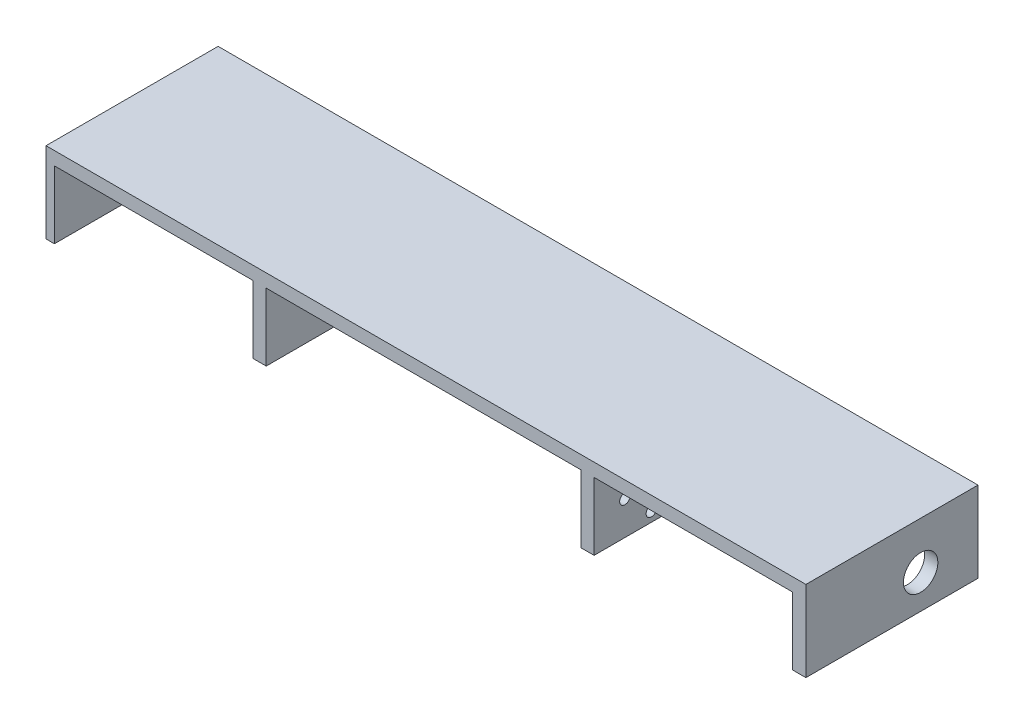
SolidWorks part; units mm, degrees
ref_plane "Front Plane" through (0, 0, 0) normal (0, 0, 1) x (1, 0, 0)
ref_plane "Top Plane" through (0, 0, 0) normal (0, 1, 0) x (1, 0, 0)
ref_plane "Right Plane" through (0, 0, 0) normal (1, 0, 0) x (0, 0, -1)
sketch "Sketch2" plane through (0, 0, 0) normal (0, 1, 0) x (1, 0, 0)
  line L1 (-42.6727, 74.2981) -> (244.3273, 74.2981)
  line L2 (-42.6727, 74.2981) -> (-42.6727, 9.2981)
  line L3 (-42.6727, 9.2981) -> (244.3273, 9.2981)
  line L4 (244.3273, 74.2981) -> (244.3273, 9.2981)
extrude "Boss-Extrude1" add sketch "Sketch2" along normal blind 5
sketch "Sketch4" plane through (0, 0, 0) normal (0, -1, 0) x (1, 0, 0)
  line L0 (-42.6727, -9.2981) -> (244.3273, -9.2981) construction
  line L1 (-42.6727, -74.2981) -> (-39.4977, -74.2981)
  line L2 (-42.6727, -74.2981) -> (-42.6727, -9.2981)
  line L3 (-42.6727, -9.2981) -> (-39.4977, -9.2981)
  line L4 (-39.4977, -74.2981) -> (-39.4977, -9.2981)
extrude "Boss-Extrude2" add sketch "Sketch4" along normal blind 25.5
sketch "Sketch5" plane through (0, 0, 0) normal (0, -1, 0) x (1, 0, 0)
  line L0 (-39.4977, -9.2981) -> (244.3273, -9.2981) construction
  line L1 (40.5023, -9.2981) -> (35.5023, -9.2981)
  line L2 (40.5023, -9.2981) -> (40.5023, -74.2981)
  line L3 (40.5023, -74.2981) -> (35.5023, -74.2981)
  line L4 (35.5023, -9.2981) -> (35.5023, -74.2981)
  line L5 (244.3273, -74.2981) -> (-39.4977, -74.2981) construction
  line L6 (-39.4977, -74.2981) -> (-39.4977, -9.2981) construction
  dimension "D1" = 80
  dimension "D2" = 5
extrude "Boss-Extrude3" add sketch "Sketch5" along normal blind 25.5 contours L2 L3 L4 L1
sketch "Sketch6" plane through (0, 0, 0) normal (0, -1, 0) x (1, 0, 0)
  line L0 (244.3273, -74.2981) -> (40.5023, -74.2981) construction
  line L1 (244.3273, -9.2981) -> (239.3273, -9.2981)
  line L2 (244.3273, -9.2981) -> (244.3273, -74.2981)
  line L3 (244.3273, -74.2981) -> (239.3273, -74.2981)
  line L4 (239.3273, -9.2981) -> (239.3273, -74.2981)
extrude "Boss-Extrude4" add sketch "Sketch6" along normal blind 25.5
sketch "Sketch7" plane through (-42.6727, 0, 0) normal (-1, 0, 0) x (0, 0, 1)
  line L0 (-9.2981, -25.5) -> (-74.2981, -25.5) construction
  line L1 (-9.2981, 5) -> (-9.2981, -25.5) construction
  circle A0 centre (-30.9648, -12.75) radius 3.5
  dimension "D3" = 7
  dimension "D1" = 12.75
  dimension "D2" = 21.6667
sketch "Sketch8" plane through (0, 0, 0) normal (0, -1, 0) x (1, 0, 0)
  line L0 (239.3273, -74.2981) -> (40.5023, -74.2981) construction
  line L1 (164.3273, -74.2981) -> (159.3273, -74.2981)
  line L2 (164.3273, -74.2981) -> (164.3273, -9.2981)
  line L3 (164.3273, -9.2981) -> (159.3273, -9.2981)
  line L4 (159.3273, -74.2981) -> (159.3273, -9.2981)
  line L5 (40.5023, -9.2981) -> (239.3273, -9.2981) construction
  line L6 (239.3273, -9.2981) -> (239.3273, -74.2981) construction
  dimension "D1" = 75
extrude "Boss-Extrude5" add sketch "Sketch8" along normal blind 25.5
sketch "Sketch9" plane through (244.3273, 0, 0) normal (1, 0, 0) x (0, 0, -1)
  line L0 (74.2981, 5) -> (74.2981, -25.5) construction
  line L1 (74.2981, -25.5) -> (9.2981, -25.5) construction
  circle A0 centre (52.6315, -12.75) radius 6.5
  dimension "D1" = 21.6667
  dimension "D2" = 12.75
extrude "Cut-Extrude1" cut sketch "Sketch7" against normal up to next
extrude "Cut-Extrude2" cut sketch "Sketch9" against normal up to next contours A0
sketch "Sketch10" plane through (35.5023, 0, 0) normal (-1, 0, 0) x (0, 0, 1)
  line L0 (-9.2981, -25.5) -> (-9.2981, 0) construction
  line L1 (-9.2981, -25.5) -> (-74.2981, -25.5) construction
  circle A0 centre (-30.9648, -12.75) radius 4.5
  dimension "D1" = 21.6667
  dimension "D2" = 12.75
sketch "Sketch11" plane through (164.3273, 0, 0) normal (1, 0, 0) x (0, 0, -1)
  line L0 (74.2981, -25.5) -> (74.2981, 0) construction
  line L1 (74.2981, -25.5) -> (9.2981, -25.5) construction
  circle A0 centre (52.6315, -12.75) radius 4.5
  dimension "D1" = 21.6667
  dimension "D2" = 12.75
extrude "Cut-Extrude3" cut sketch "Sketch11" against normal up to next
extrude "Cut-Extrude4" cut sketch "Sketch10" against normal up to next contours A0
sketch "Sketch14" plane through (159.3273, 0, 0) normal (-1, 0, 0) x (0, 0, 1)
  line L0 (-9.2981, -25.5) -> (-9.2981, 0) construction
  line L1 (-9.2981, -25.5) -> (-74.2981, -25.5) construction
  line L2 (-15.9681, -25.5) -> (-14.9681, -25.5)
  line L3 (-15.9681, -25.5) -> (-15.9681, 0)
  line L4 (-15.9681, 0) -> (-14.9681, 0)
  line L5 (-14.9681, -25.5) -> (-14.9681, 0)
  line L6 (-9.2981, 0) -> (-74.2981, 0) construction
  line L8 (-46.9681, -25.5) -> (-45.9681, -25.5)
  line L9 (-46.9681, -25.5) -> (-46.9681, 0)
  line L10 (-46.9681, 0) -> (-45.9681, 0)
  line L11 (-45.9681, -25.5) -> (-45.9681, 0)
  point P0 (-30.9681, -11.7464)
  dimension "D1" = 21.67
  dimension "D2" = 15
  dimension "D3" = 15
extrude "Boss-Extrude6" add sketch "Sketch14" along normal blind 1
sketch "Sketch15" plane through (159.3273, 0, 0) normal (-1, 0, 0) x (0, 0, 1)
  line L0 (-15.9681, 0) -> (-45.9681, 0) construction
  line L1 (-15.9681, 0) -> (-15.9681, -25.5) construction
  line L2 (-45.9681, -25.5) -> (-45.9681, 0) construction
  line L4 (-15.9681, -25.5) -> (-45.9681, -25.5) construction
  circle A0 centre (-20.9681, -12.75) radius 2
  circle A1 centre (-40.9681, -12.75) radius 2
  circle A2 centre (-30.9681, -21.75) radius 2
  circle A3 centre (-30.9681, -3.75) radius 2
  dimension "D2" = 5
  dimension "D3" = 5
  dimension "D4" = 15
  dimension "D6" = 3.75
  dimension "D7" = 4
  dimension "D1" = 12.75
  dimension "D5" = 3.75
extrude "Cut-Extrude6" cut sketch "Sketch15" against normal up to next
